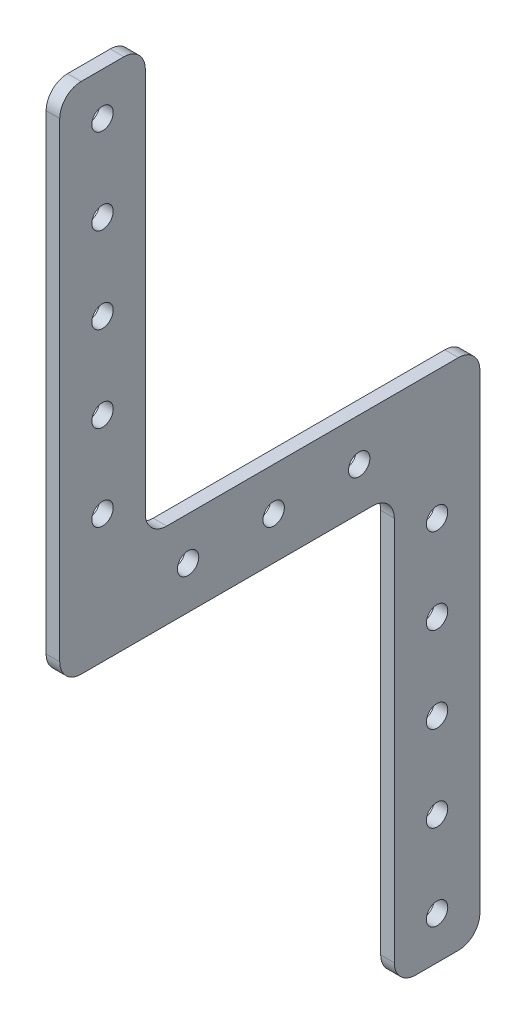
SolidWorks part; units mm, degrees
ref_plane "Front Plane" through (0, 0, 0) normal (0, 0, 1) x (1, 0, 0)
ref_plane "Top Plane" through (0, 0, 0) normal (0, 1, 0) x (1, 0, 0)
ref_plane "Right Plane" through (0, 0, 0) normal (1, 0, 0) x (0, 0, -1)
sketch "Sketch2" plane through (0, 0, 0) normal (1, 0, 0) x (0, 0, -1)
  line L0 (-49.1, 110) -> (-29.1, 110)
  line L1 (-29.1, 110) -> (-29.1, 10)
  line L2 (-29.1, 10) -> (49.1, 10)
  line L3 (49.1, 10) -> (49.1, -110)
  line L4 (49.1, -110) -> (29.1, -110)
  line L5 (29.1, -110) -> (29.1, -10)
  line L6 (29.1, -10) -> (-49.1, -10)
  line L7 (-49.1, -10) -> (-49.1, 110)
  line L8 (-39.1, 100) -> (-39.1, 80) construction
  line L9 (39.1, -100) -> (39.1, -80) construction
  line L10 (-19.1, 0) -> (0.9, 0) construction
  circle A0 centre (-39.1, 100) radius 2.5
  circle A1 centre (-39.1, 80) radius 2.5
  circle A2 centre (-39.1, 60) radius 2.5
  circle A3 centre (-39.1, 40) radius 2.5
  circle A4 centre (-39.1, 20) radius 2.5
  circle A6 centre (39.1, -100) radius 2.5
  circle A7 centre (39.1, -80) radius 2.5
  circle A8 centre (39.1, -60) radius 2.5
  circle A9 centre (39.1, -40) radius 2.5
  circle A10 centre (39.1, -20) radius 2.5
  circle A13 centre (-19.1, 0) radius 2.5
  circle A14 centre (0.9, 0) radius 2.5
  circle A15 centre (20.9, 0) radius 2.5
  point P25 (39.1, -110)
  dimension "D9" = 5
  dimension "D1" = 20
  dimension "D2" = 20
  dimension "D3" = 120
  dimension "D4" = 98.2
  dimension "D5" = 49.1
  dimension "D6" = 10
  dimension "D7" = 10
  dimension "D8" = 10
  dimension "D11" = 20
  dimension "D12" = 10
  dimension "D14" = 20
  dimension "D15" = 10
  dimension "D17" = 20
  dimension "D10" = 5
  dimension "D13" = 5
  dimension "D16" = 3
extrude "Boss-Extrude1" add sketch "Sketch2" along normal blind 3.175
fillet "Fillet1" radius 5 8 edges at (1.5875, -110, -49.1) (1.5875, -110, -29.1) (1.5875, -10, -29.1) (1.5875, 10, -49.1) (1.5875, 10, 29.1) (1.5875, -10, 49.1) (1.5875, 110, 29.1) (1.5875, 110, 49.1)
equation "\"D2@Sketch2\"=\"D1@Sketch2\""
equation "\"D5@Sketch2\"=\"D4@Sketch2\"/2"
